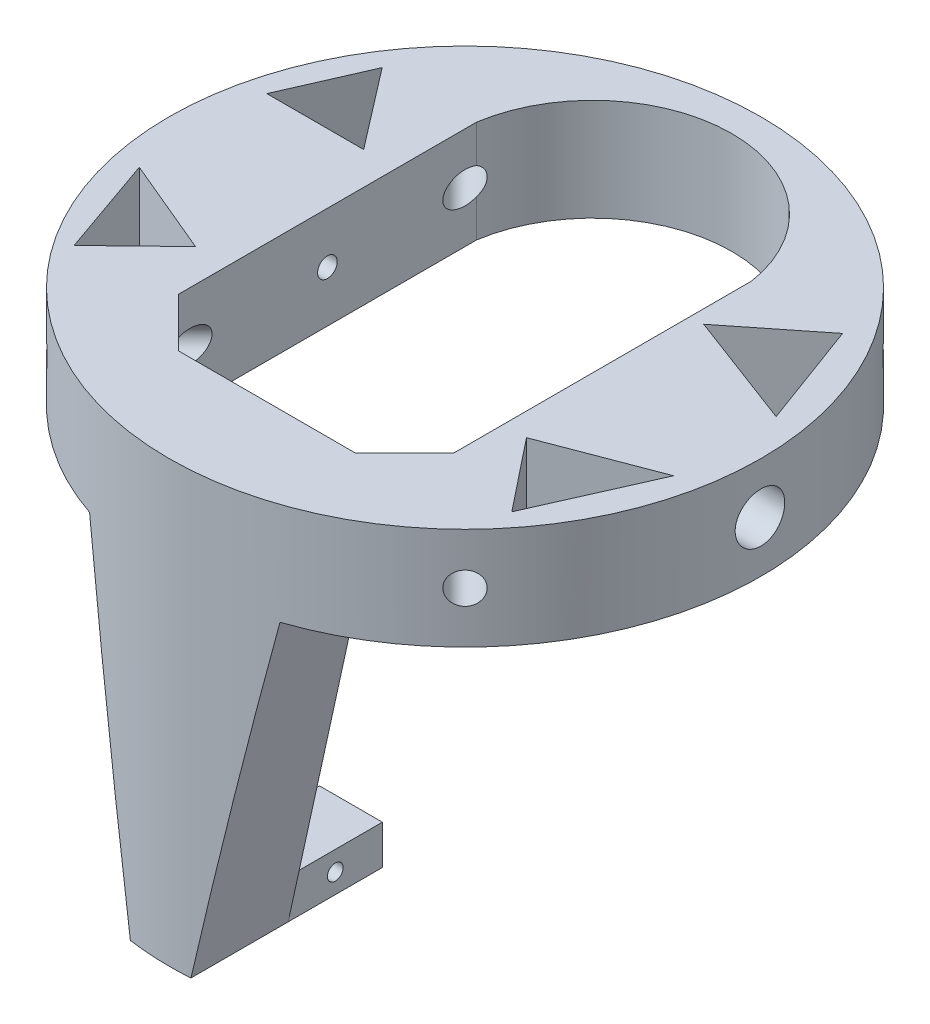
SolidWorks part; units mm, degrees
ref_plane "Front Plane" through (0, 0, 0) normal (0, 0, 1) x (1, 0, 0)
ref_plane "Top Plane" through (0, 0, 0) normal (0, 1, 0) x (1, 0, 0)
ref_plane "Right Plane" through (0, 0, 0) normal (1, 0, 0) x (0, 0, -1)
sketch "Sketch2" plane through (0, 0, 0) normal (0, 1, 0) x (1, 0, 0)
  line L16 (50.7713, -30.1697) -> (50.7713, 7.8303)
  line L17 (50.7713, 7.8303) -> (56.9939, 14.0529)
  line L18 (56.9939, 14.0529) -> (79.5939, 14.0529)
  line L19 (79.5939, 14.0529) -> (85.8164, 7.8303)
  line L20 (85.8164, 7.8303) -> (85.8164, -30.1697)
  line L21 (85.8164, -30.1697) -> (79.5939, -36.3922)
  line L22 (79.5939, -36.3922) -> (56.9939, -36.3922)
  line L23 (56.9939, -36.3922) -> (50.7713, -30.1697)
  line L24 (56.1654, 16.0529) -> (80.4223, 16.0529)
  line L25 (80.4223, 16.0529) -> (87.8164, 8.6588)
  line L26 (87.8164, 8.6588) -> (87.8164, -30.9981)
  line L27 (87.8164, -30.9981) -> (80.4223, -38.3922)
  line L28 (80.4223, -38.3922) -> (56.1654, -38.3922)
  line L29 (56.1654, -38.3922) -> (48.7713, -30.9981)
  line L30 (48.7713, -30.9981) -> (48.7713, 8.6588)
  line L31 (48.7713, 8.6588) -> (56.1654, 16.0529)
  dimension "D2" = 22.6
  dimension "D3" = 8.8
  dimension "D4" = 38
  dimension "D5" = 8.8
  dimension "D6" = 38
  dimension "D7" = 8.8
  dimension "D1" = 2
extrude "Boss-Extrude1" add sketch "Sketch2" along normal blind 13
sketch "Sketch3" plane through (0, 0, 38.3922) normal (0, 0, 1) x (1, 0, 0)
  line L0 (56.1654, 13) -> (80.4223, 13) construction
  circle A0 centre (68.9867, 6.5) radius 1.2
  dimension "D1" = 6.5
sketch "Sketch4" plane through (0, 0, 0) normal (0, -1, 0) x (1, 0, 0)
  line L0 (56.9939, 36.3922) -> (79.5939, 36.3922) construction
  line L1 (62.9939, 36.3922) -> (70.9939, 36.3922)
  line L2 (62.9939, 36.3922) -> (62.9939, 38.3922)
  line L3 (62.9939, 38.3922) -> (70.9939, 38.3922)
  line L4 (70.9939, 36.3922) -> (70.9939, 38.3922)
  line L5 (56.1654, 38.3922) -> (80.4223, 38.3922) construction
  dimension "D1" = 6
  dimension "D2" = 8
extrude "Boss-Extrude2" add sketch "Sketch4" along normal blind 43
sketch "Sketch5" plane through (0, 0, 36.3922) normal (0, 0, -1) x (-1, 0, 0)
  line L0 (-70.9939, -43) -> (-70.9939, 0) construction
  line L1 (-70.9939, -10) -> (-62.9939, -10)
  line L2 (-70.9939, -10) -> (-70.9939, -15)
  line L3 (-70.9939, -15) -> (-62.9939, -15)
  line L4 (-62.9939, -10) -> (-62.9939, -15)
  line L5 (-62.9939, -43) -> (-62.9939, 0) construction
  line L7 (-70.9939, -38) -> (-62.9939, -38)
  line L8 (-70.9939, -38) -> (-70.9939, -43)
  line L9 (-70.9939, -43) -> (-62.9939, -43)
  line L10 (-62.9939, -38) -> (-62.9939, -43)
  dimension "D1" = 5
  dimension "D2" = 5
  dimension "D3" = 23
  dimension "D4" = 10
extrude "Boss-Extrude3" add sketch "Sketch5" along normal blind 12
sketch "Sketch6" plane through (62.9939, 0, 0) normal (-1, 0, 0) x (0, 0, 1)
  line L0 (24.3922, -10) -> (36.3922, -10) construction
  line L1 (24.3922, -15) -> (24.3922, -10) construction
  line L2 (24.3922, -43) -> (24.3922, -38) construction
  circle A0 centre (30.3922, -12.5) radius 1
  circle A1 centre (30.3922, -40.5) radius 1
  dimension "D1" = 2.5
  dimension "D3" = 6
  dimension "D2" = 6
extrude "Cut-Extrude3" cut sketch "Sketch6" against normal blind 13 contours A0 | A1
fillet "Fillet1" radius 10 1 edges at (66.9939, -10, 36.3922)
sketch "Sketch10" plane through (0, 0, 38.3922) normal (0, 0, 1) x (1, 0, 0)
  line L0 (56.1654, 0) -> (62.9939, -43)
  line L1 (62.9939, -43) -> (70.9939, -43)
  line L2 (70.9939, -43) -> (80.4223, 0)
  line L3 (80.4223, 0) -> (56.1654, 0)
extrude "Boss-Extrude4" add sketch "Sketch10" against normal blind 2
sketch "Sketch11" plane through (0, 13, 0) normal (0, 1, 0) x (1, 0, 0)
  line L0 (68.2939, 14.0529) -> (68.2939, -36.3922)
  line L1 (79.5939, 14.0529) -> (56.9939, 14.0529) construction
  line L2 (56.9939, -36.3922) -> (79.5939, -36.3922) construction
  line L3 (56.1654, 16.0529) -> (48.7713, 8.6588)
  line L4 (48.7713, 8.6588) -> (48.7713, -30.9981)
  line L5 (48.7713, -30.9981) -> (56.1654, -38.3922)
  line L6 (56.1654, -38.3922) -> (80.4223, -38.3922)
  line L7 (80.4223, -38.3922) -> (87.8164, -30.9981)
  line L8 (87.8164, -30.9981) -> (87.8164, 8.6588)
  line L9 (87.8164, 8.6588) -> (80.4223, 16.0529)
  line L10 (80.4223, 16.0529) -> (56.1654, 16.0529)
  circle A0 centre (68.2939, -11.1697) radius 37.7
  point P23 (0, 0)
  point P26 (0, 0)
  point P27 (0, 0)
  point P28 (0, 0)
  dimension "D1" = 75.4
extrude "Boss-Extrude5" add sketch "Sketch11" against normal blind 13 contours L10 L3 L4 L5 L6 L7 L8 L9 | A0
ref_plane "Plane1" through (105.9939, 0, 0) normal (1, 0, 0) x (0, 0, -1)
sketch "Sketch19" plane through (0, 13, 0) normal (0, 1, 0) x (1, 0, 0)
  line L0 (85.8164, -11.1697) -> (105.9939, -11.1697)
  line L1 (85.8164, -30.1697) -> (85.8164, 7.8303) construction
  circle A0 centre (68.2939, -11.1697) radius 37.7 construction
sketch "Sketch22" plane through (105.9939, 0, 0) normal (1, 0, 0) x (0, 0, -1)
  line L0 (-11.1697, 13) -> (-11.1697, 0) construction
  line L1 (-30.1697, 13) -> (7.8303, 13) construction
  line L2 (-48.8697, 0) -> (26.5303, 0) construction
  circle A0 centre (-11.1697, 6.5) radius 3.1558
  circle A1 centre (-11.1697, 6.5) radius 1.25
extrude "Cut-Extrude6" cut sketch "Sketch22" against normal blind 83 contours A1
extrude "Cut-Extrude7" cut sketch "Sketch22<3>" against normal blind 15
sketch "Sketch22<3>" plane through (105.9939, 0, 0) normal (1, 0, 0) x (0, 0, -1) same geometry as "Sketch22"
ref_plane "Plane2" through (30.5939, 0, 0) normal (-1, 0, 0) x (0, 0, 1)
sketch "Sketch23" plane through (30.5939, 0, 0) normal (-1, 0, 0) x (0, 0, 1)
  circle A0 centre (11.1697, 6.5) radius 3
extrude "Cut-Extrude8" cut sketch "Sketch23" against normal blind 15
sketch "Sketch25" plane through (0, 0, 38.3922) normal (0, 0, 1) x (1, 0, 0)
  line L4 (80.4223, 0) -> (56.1654, 0)
  line L5 (56.1654, 0) -> (62.9939, -43)
  line L6 (62.9939, -43) -> (70.9939, -43)
  line L7 (70.9939, -43) -> (80.4223, 0)
  line L8 (80.4223, 0) -> (56.1654, 0)
  line L9 (56.1654, 0) -> (62.9939, -43)
  line L10 (62.9939, -43) -> (70.9939, -43)
  line L11 (70.9939, -43) -> (80.4223, 0)
  dimension "D1" = 0
extrude "Boss-Extrude6" add sketch "Sketch25" along normal up to surface (10.1031 mm away) up to face at (30.7073, 5.8207, 8.2476)
ref_plane "Plane3" through (1.9042, 0, -1.9042) normal (-0.7071, 0, 0.7071) x (0.7071, 0, 0.7071)
sketch "Sketch26" plane through (1.9042, 0, -1.9042) normal (-0.7071, 0, 0.7071) x (0.7071, 0, 0.7071)
  line L0 (56.1892, 13) -> (56.1892, 0) construction
  line L1 (93.8892, 13) -> (18.4892, 13) construction
  line L2 (18.4892, 0) -> (93.8892, 0) construction
  circle A0 centre (56.1892, 6.5) radius 2
extrude "Cut-Extrude9" cut sketch "Sketch26" against normal blind 88
ref_plane "Plane4" through (66.3897, 0, 66.3897) normal (0.7071, 0, 0.7071) x (0.7071, 0, -0.7071)
sketch "Sketch27" plane through (66.3897, 0, 66.3897) normal (0.7071, 0, 0.7071) x (0.7071, 0, -0.7071)
  line L0 (40.3929, 13) -> (40.3929, 0) construction
  line L1 (78.0929, 13) -> (2.6929, 13) construction
  line L2 (2.6929, 0) -> (78.0929, 0) construction
  circle A0 centre (40.3929, 6.5) radius 2
extrude "Cut-Extrude10" cut sketch "Sketch27" against normal blind 120
sketch "Sketch28" plane through (0, 0, 0) normal (0, -1, 0) x (1, 0, 0)
  line L0 (85.8164, 30.1697) -> (85.8164, -7.8303) construction
  line L1 (85.8164, 23.8011) -> (91.7008, 23.8011)
  line L2 (85.8164, 23.8011) -> (85.8164, 0)
  line L3 (85.8164, 0) -> (91.7008, 0)
  line L4 (91.7008, 23.8011) -> (91.7008, 0)
extrude "Cut-Extrude11" cut sketch "Sketch28" against normal blind 2.5
sketch "Sketch30" plane through (0, 0, 0) normal (0, -1, 0) x (1, 0, 0)
  line L0 (50.7713, -7.8303) -> (85.8164, -7.8303)
  line L1 (38.7417, -7.8303) -> (34.2664, 2.3859)
  line L2 (34.2664, 2.3859) -> (46.5977, 2.3859)
  line L3 (46.5977, 2.3859) -> (38.7417, -7.8303)
  line L4 (97.3898, -7.8303) -> (87.5329, 0)
  line L5 (85.8164, 0) -> (91.7008, 0) construction
  line L6 (87.5329, 0) -> (102.3322, 5.5784)
  line L7 (102.3322, 5.5784) -> (97.3898, -7.8303)
  line L8 (102.3322, 18.6293) -> (88.7586, 23.8011)
  line L9 (91.7008, 23.8011) -> (85.8164, 23.8011) construction
  line L10 (88.7586, 23.8011) -> (95.999, 32.9153)
  line L11 (95.999, 32.9153) -> (102.3322, 18.6293)
  line L12 (34.2664, 18.6293) -> (38.7417, 31.4107)
  line L13 (38.7417, 31.4107) -> (46.5977, 23.8011)
  line L14 (46.5977, 23.8011) -> (34.2664, 18.6293)
  arc A0 (50.7713, -7.8303) -> (85.8164, -7.8303) centre (68.2939, -5.0913) ccw
extrude "Cut-Extrude12" cut sketch "Sketch30" against normal up to next
